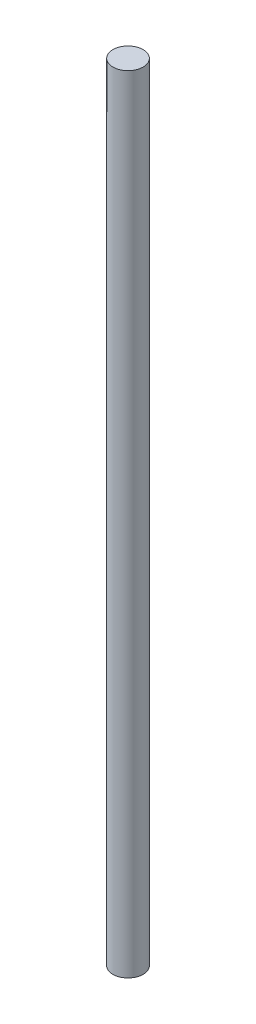
SolidWorks part; units mm, degrees
material "1060 Alloy"
ref_plane "Front Plane" through (0, 0, 0) normal (0, 0, 1) x (1, 0, 0)
ref_plane "Top Plane" through (0, 0, 0) normal (0, 1, 0) x (1, 0, 0)
ref_plane "Right Plane" through (0, 0, 0) normal (1, 0, 0) x (0, 0, -1)
sketch "Sketch1" plane through (0, 0, 0) normal (0, 0, 1) x (1, 0, 0)
  line L1 (0, 0) -> (6.35, 0)
  line L2 (0, 0) -> (0, 330.2)
  line L3 (0, 330.2) -> (6.35, 330.2)
  line L4 (6.35, 0) -> (6.35, 330.2)
  dimension "D1" = 330.2
  dimension "D2" = 6.35
revolve "Revolve1" add sketch "Sketch1" angle 360 about L2
